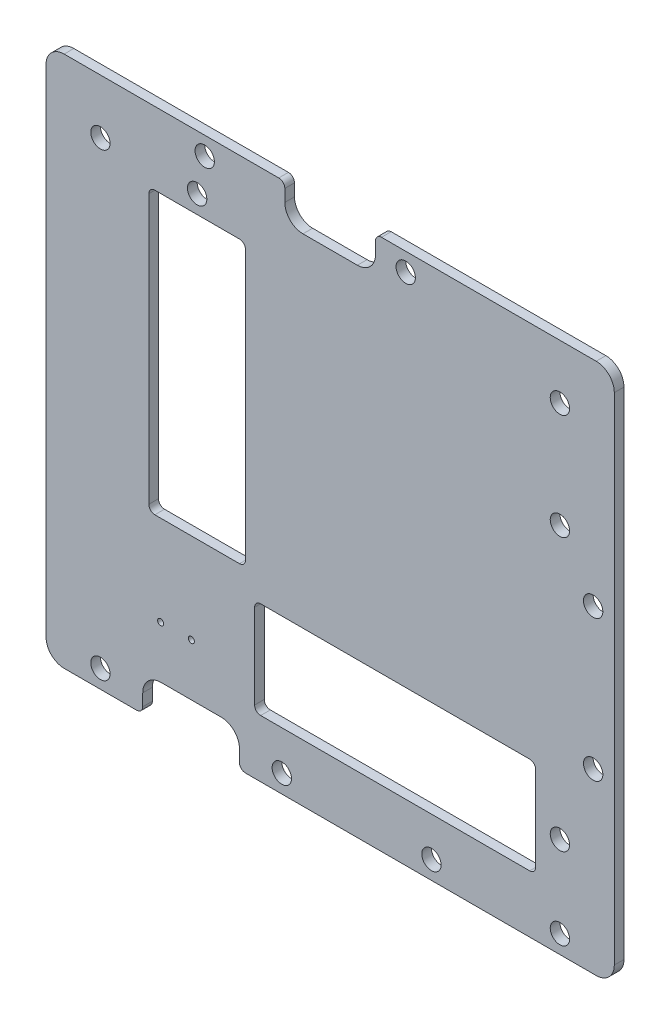
SolidWorks part; units mm, degrees
ref_plane "Front Plane" through (0, 0, 0) normal (0, 0, 1) x (1, 0, 0)
ref_plane "Top Plane" through (0, 0, 0) normal (0, 1, 0) x (1, 0, 0)
ref_plane "Right Plane" through (0, 0, 0) normal (1, 0, 0) x (0, 0, -1)
sketch "Sketch1" plane through (0, 0, 0) normal (0, 0, 1) x (1, 0, 0)
  line L0 (-6.5653, 21.4519) -> (-53.0653, 21.4519) construction
  line L1 (-87.5653, 88.9519) -> (-87.5653, 6.9519)
  line L2 (6.4347, 88.9519) -> (6.4347, 6.9519)
  line L3 (-84.5653, 91.9519) -> (-48.0653, 91.9519)
  line L4 (-62.5653, 33.4519) -> (-62.5653, 79.9519) construction
  line L5 (-40.5653, 3.9519) -> (-40.5653, 85.9519) construction
  line L6 (-33.0653, 91.9519) -> (-33.0653, 85.9519)
  line L7 (-84.5653, 3.9519) -> (-71.5653, 3.9519)
  line L8 (-33.0653, 85.9519) -> (-48.0653, 85.9519)
  line L9 (-53.0653, 13.4519) -> (-6.5653, 13.4519)
  line L10 (-53.0653, 13.4519) -> (-53.0653, 29.4519)
  line L11 (-53.0653, 29.4519) -> (-6.5653, 29.4519)
  line L12 (-6.5653, 13.4519) -> (-6.5653, 29.4519)
  line L13 (-53.0653, 13.4519) -> (-6.5653, 29.4519) construction
  line L14 (-53.0653, 29.4519) -> (-6.5653, 13.4519) construction
  line L15 (-48.0653, 85.9519) -> (-48.0653, 91.9519)
  line L16 (-70.5653, 33.4519) -> (-54.5653, 33.4519)
  line L17 (-70.5653, 33.4519) -> (-70.5653, 79.9519)
  line L18 (-70.5653, 79.9519) -> (-54.5653, 79.9519)
  line L19 (-54.5653, 33.4519) -> (-54.5653, 79.9519)
  line L20 (-70.5653, 33.4519) -> (-54.5653, 79.9519) construction
  line L21 (-70.5653, 79.9519) -> (-54.5653, 33.4519) construction
  line L22 (-33.0653, 91.9519) -> (3.4347, 91.9519)
  line L23 (-71.5653, 3.9519) -> (-71.5653, 9.9519)
  line L24 (-71.5653, 9.9519) -> (-55.5653, 9.9519)
  line L25 (-55.5653, 9.9519) -> (-55.5653, 3.9519)
  line L26 (-55.5653, 3.9519) -> (3.4347, 3.9519)
  arc A0 (3.4347, 3.9519) -> (6.4347, 6.9519) centre (3.4347, 6.9519) ccw
  arc A1 (-84.5653, 3.9519) -> (-87.5653, 6.9519) centre (-84.5653, 6.9519) cw
  arc A2 (-84.5653, 91.9519) -> (-87.5653, 88.9519) centre (-84.5653, 88.9519) ccw
  arc A3 (3.4347, 91.9519) -> (6.4347, 88.9519) centre (3.4347, 88.9519) cw
  circle A4 centre (-63.5253, 18.5519) radius 0.5
  circle A5 centre (-68.6053, 18.5519) radius 0.5
  dimension "D5" = 3
  dimension "D7" = 8
  dimension "D6" = 3
  dimension "D9" = 88
  dimension "D10" = 3
  dimension "D13" = 25
  dimension "D14" = 12
  dimension "D4" = 3
  dimension "D2" = 88
  dimension "D3" = 94
  dimension "D8" = 46.5
  dimension "D11" = 46.5
  dimension "D12" = 8
  dimension "D15" = 17.5
  dimension "D16" = 13
  dimension "D17" = 7.5
  dimension "D18" = 6
  dimension "D19" = 6
  dimension "D20" = 16
  dimension "D21" = 32
extrude "Boss-Extrude1" add sketch "Sketch1" along normal blind 1.6
hole_wizard "Ø3.2 (3.2) Diameter Hole3" positions "Sketch7" profile "Sketch6" hole size "Ø3.2" standard "Ansi Metric" end condition up to next
sketch "Sketch7" plane through (0, 0, 0) normal (0, 0, -1) x (-1, 0, 0)
  line L2 (-6.4347, 6.9519) -> (-6.4347, 88.9519) construction
  line L4 (87.5653, 47.9519) -> (-6.4347, 47.9519) construction
  line L5 (87.5653, 88.9519) -> (87.5653, 6.9519) construction
  line L6 (40.5653, 85.9519) -> (40.5653, 3.9519) construction
  line L8 (78.5653, 82.9519) -> (78.5653, 6.9519) construction
  line L10 (24.8153, 6.9519) -> (22.8153, 6.9519) construction
  line L11 (60.3153, 88.9519) -> (62.3153, 88.9519) construction
  line L15 (33.0653, 85.9519) -> (48.0653, 85.9519) construction
  line L16 (-3.4347, 91.9519) -> (33.0653, 91.9519) construction
  point P6 (78.5653, 6.9519)
  point P9 (78.5653, 82.9519)
  point P12 (2.5653, 82.9519)
  point P15 (2.5653, 6.9519)
  point P38 (2.5653, 65.4519)
  point P40 (2.5653, 20.4519)
  point P53 (62.5653, 82.9519)
  point P68 (48.5653, 6.9519)
  point P78 (28.0653, 88.9519)
  point P79 (61.3153, 88.9519)
  point P81 (-2.9347, 56.6185)
  point P83 (-2.9347, 33.2852)
  point P102 (23.8153, 6.9519)
  dimension "D1" = 35
  dimension "D2" = 38
  dimension "D3" = 38
  dimension "D4" = 35
  dimension "D5" = 41
  dimension "D6" = 38
  dimension "D7" = 38
  dimension "D8" = 58.6667
  dimension "D9" = 38
  dimension "D10" = 38
  dimension "D11" = 17.5
  dimension "D12" = 27.5
  dimension "D13" = 35
  dimension "D14" = 22
  dimension "D15" = 8
  dimension "D16" = 41
  dimension "D17" = 41
  dimension "D18" = 12.5
  dimension "D19" = 35.3333
sketch "Sketch6" plane through (-78.5653, 6.9519, 0) normal (1, 0, 0) x (0, 1, 0)
  line L0 (0, 0) -> (0, 1.6)
  line L1 (0, 1.6) -> (1.6, 1.6)
  line L2 (1.6, 1.6) -> (1.6, 0)
  line L5 (1.6, 0) -> (0, 0)
  line L11 (0, -6.35) -> (0, 107.95) construction
  dimension "Thru Hole Dia." = 3.2
  dimension "Thru Hole Depth" = 1.6
fillet "Fillet1" radius 3 4 edges at (-48.0653, 85.9519, 0.8) (-33.0653, 85.9519, 0.8) (-55.5653, 9.9519, 0.8) (-71.5653, 9.9519, 0.8)
fillet "Fillet2" radius 1 12 edges at (-6.5653, 13.4519, 0.8) (-6.5653, 29.4519, 0.8) (-53.0653, 29.4519, 0.8) (-53.0653, 13.4519, 0.8) (-70.5653, 33.4519, 0.8) (-54.5653, 33.4519, 0.8) (-54.5653, 79.9519, 0.8) (-70.5653, 79.9519, 0.8) (-48.0653, 91.9519, 0.8) (-33.0653, 91.9519, 0.8) (-55.5653, 3.9519, 0.8) (-71.5653, 3.9519, 0.8)
